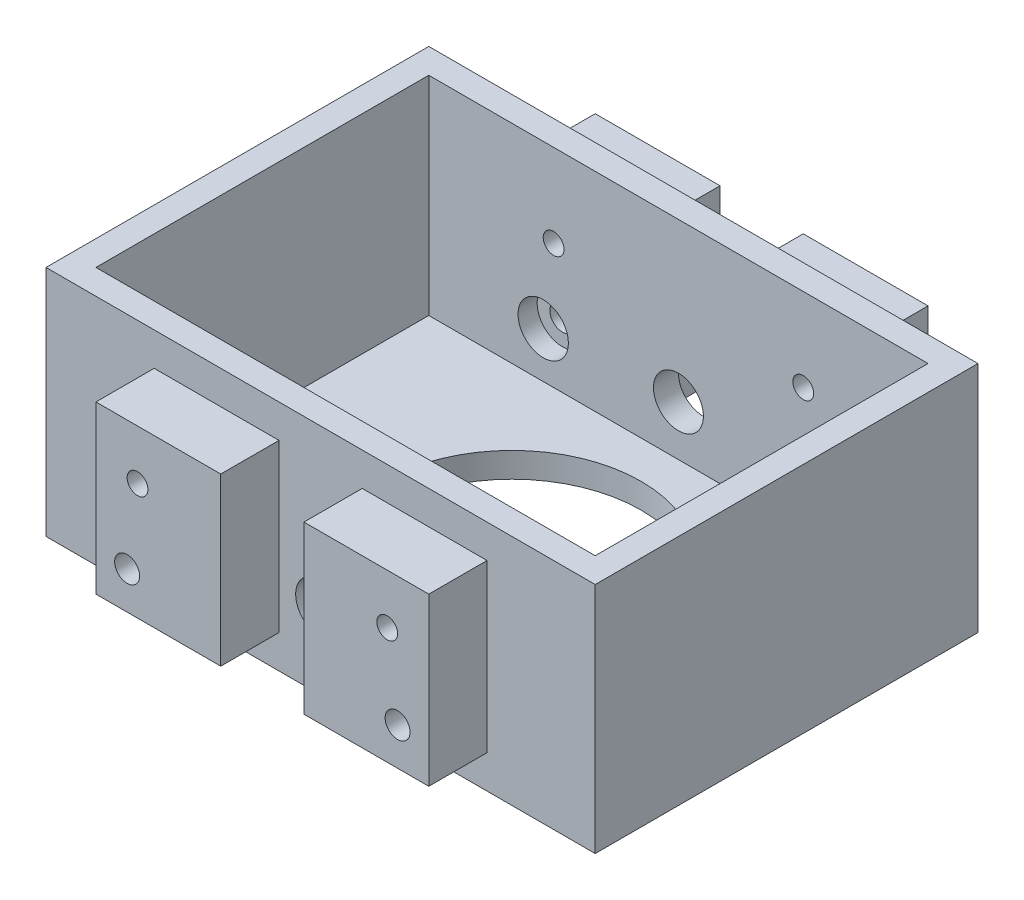
SolidWorks part; units mm, degrees
ref_plane "Front Plane" through (0, 0, 0) normal (0, 0, 1) x (1, 0, 0)
ref_plane "Top Plane" through (0, 0, 0) normal (0, 1, 0) x (1, 0, 0)
ref_plane "Right Plane" through (0, 0, 0) normal (1, 0, 0) x (0, 0, -1)
sketch "Sketch1" plane through (0, 0, 0) normal (0, 1, 0) x (1, 0, 0)
  line L1 (-41.3246, 5.1822) -> (24.6754, 5.1822)
  line L2 (-41.3246, 5.1822) -> (-41.3246, -40.8178)
  line L3 (-41.3246, -40.8178) -> (24.6754, -40.8178)
  line L4 (24.6754, 5.1822) -> (24.6754, -40.8178)
  dimension "D1" = 66
  dimension "D2" = 46
extrude "Boss-Extrude2" add sketch "Sketch1" along normal blind 3
sketch "Sketch3" plane through (0, 3, 0) normal (0, 1, 0) x (1, 0, 0)
  line L0 (-41.3246, 5.1822) -> (-41.3246, -40.8178) construction
  line L1 (-41.3246, 5.1822) -> (-38.3246, 5.1822)
  line L2 (-41.3246, 5.1822) -> (-41.3246, -40.8178)
  line L3 (-41.3246, -40.8178) -> (-38.3246, -40.8178)
  line L4 (-38.3246, 5.1822) -> (-38.3246, -40.8178)
  line L5 (-38.3246, 5.1822) -> (21.6754, 5.1822)
  line L6 (-38.3246, 5.1822) -> (-38.3246, 2.1822)
  line L7 (-38.3246, 2.1822) -> (21.6754, 2.1822)
  line L8 (21.6754, 5.1822) -> (21.6754, 2.1822)
  line L9 (21.6754, 5.1822) -> (24.6754, 5.1822)
  line L10 (21.6754, 5.1822) -> (21.6754, -40.8178)
  line L11 (21.6754, -40.8178) -> (24.6754, -40.8178)
  line L12 (24.6754, 5.1822) -> (24.6754, -40.8178)
  line L13 (-38.3246, -37.8178) -> (21.6754, -37.8178)
  line L14 (-38.3246, -37.8178) -> (-38.3246, -40.8178)
  line L15 (-38.3246, -40.8178) -> (21.6754, -40.8178)
  line L16 (21.6754, -37.8178) -> (21.6754, -40.8178)
  line L17 (24.6754, 5.1822) -> (-41.3246, 5.1822) construction
  line L18 (-41.3246, -40.8178) -> (24.6754, -40.8178) construction
  line L19 (24.6754, -40.8178) -> (24.6754, 5.1822) construction
  point P22 (23.1754, -40.8178)
  dimension "D1" = 3
  dimension "D2" = 3
  dimension "D3" = 3
  dimension "D4" = 3
  dimension "D5" = 0
  dimension "D6" = 0
  dimension "D7" = 0
  dimension "D8" = 0
  dimension "D9" = 0
  dimension "D10" = 0
  dimension "D11" = 0
  dimension "D12" = 0
  dimension "D13" = 0
  dimension "D14" = 0
  dimension "D15" = 0
  dimension "D16" = 0
extrude "Boss-Extrude4" add sketch "Sketch3" along normal blind 25 contours L8 L19 L4 L7 | L4 L19 L0 L17 | L13 L16 L15 L14 | L12 L11 L10 L9 region at (-39.8246, 3, 17.8178) region at (-8.3246, 3, -3.6822)
sketch "Sketch4" plane through (0, 0, 40.8178) normal (0, 0, 1) x (1, 0, 0)
  line L0 (24.6754, 28) -> (24.6754, 0) construction
  line L1 (-13.3246, 24) -> (-28.3246, 24)
  line L2 (-13.3246, 24) -> (-13.3246, 4)
  line L3 (-13.3246, 4) -> (-28.3246, 4)
  line L4 (-28.3246, 24) -> (-28.3246, 4)
  line L5 (-3.3246, 24) -> (11.6754, 24)
  line L6 (-3.3246, 24) -> (-3.3246, 4)
  line L7 (-3.3246, 4) -> (11.6754, 4)
  line L8 (11.6754, 24) -> (11.6754, 4)
  line L10 (-41.3246, 0) -> (24.6754, 0) construction
  line L11 (-41.3246, 28) -> (24.6754, 28) construction
  dimension "D1" = 15
  dimension "D2" = 20
  dimension "D3" = 15
  dimension "D4" = 20
  dimension "D5" = 10
  dimension "D6" = 13
  dimension "D7" = 4
  dimension "D8" = 4
extrude "Boss-Extrude5" add sketch "Sketch4" along normal blind 7 contours L8 L5 L6 L7 | L2 L1 L4 L3 region at (4.1754, 14, 40.8178)
sketch "Sketch5" plane through (0, 0, 47.8178) normal (0, 0, 1) x (1, 0, 0)
  line L0 (-41.3246, 28) -> (-41.3246, 0) construction
  line L1 (-41.3246, 28) -> (24.6754, 28) construction
  line L3 (24.6754, 28) -> (24.6754, 0) construction
  circle A2 centre (-24.5746, 8.5) radius 1.5
  circle A3 centre (7.9254, 8.5) radius 1.5
  circle A4 centre (6.6754, 18) radius 1.25
  circle A5 centre (-23.3246, 18) radius 1.25
  dimension "D5" = 16.75
  dimension "D9" = 3
  dimension "D10" = 2.5
  dimension "D11" = 3
  dimension "D12" = 2.5
  dimension "D1" = 32.5
  dimension "D2" = 30
  dimension "D3" = 9.5
  dimension "D4" = 9.5
  dimension "D6" = 10
  dimension "D7" = 16.75
  dimension "D8" = 18
extrude "Cut-Extrude1" cut sketch "Sketch5" against normal up to next
sketch "Sketch6" plane through (0, 0, -5.1822) normal (0, 0, -1) x (-1, 0, 0)
  line L0 (3.3246, 24) -> (-11.6754, 24)
  line L5 (3.3246, 24) -> (3.3246, 4)
  line L6 (3.3246, 4) -> (-11.6754, 4)
  line L7 (-11.6754, 24) -> (-11.6754, 4)
  line L8 (13.3246, 24) -> (28.3246, 24)
  line L9 (13.3246, 24) -> (13.3246, 4)
  line L10 (13.3246, 4) -> (28.3246, 4)
  line L11 (28.3246, 24) -> (28.3246, 4)
  line L13 (-24.6754, 28) -> (41.3246, 28) construction
  line L14 (41.3246, 28) -> (41.3246, 0) construction
  dimension "D1" = 20
  dimension "D2" = 15
  dimension "D3" = 15
  dimension "D4" = 20
  dimension "D5" = 10
  dimension "D6" = 4
  dimension "D7" = 13
  dimension "D8" = 4
extrude "Boss-Extrude6" add sketch "Sketch6" along normal blind 7 contours L0 L7 L6 L5 | L8 L11 L10 L9 region at (4.1754, 14, -5.1822)
sketch "Sketch7" plane through (0, 0, -12.1822) normal (0, 0, -1) x (-1, 0, 0)
  line L1 (-24.6754, 28) -> (-24.6754, 0) construction
  line L3 (-24.6754, 28) -> (41.3246, 28) construction
  circle A1 centre (-7.9254, 8.5) radius 1.5
  circle A2 centre (24.5746, 8.5) radius 1.5
  circle A3 centre (23.3246, 18) radius 1.25
  circle A4 centre (-6.6754, 18) radius 1.25
  dimension "D5" = 2.5
  dimension "D6" = 3
  dimension "D7" = 2.5
  dimension "D8" = 3
  dimension "D9" = 16.75
  dimension "D10" = 10
  dimension "D11" = 18
  dimension "D12" = 10
  dimension "D1" = 32.5
  dimension "D2" = 9.5
  dimension "D3" = 9.5
  dimension "D4" = 30
extrude "Cut-Extrude2" cut sketch "Sketch7" against normal blind 10
sketch "Sketch8" plane through (0, 0, 0) normal (0, -1, 0) x (-1, 0, 0)
  line L0 (-24.6754, 5.1822) -> (41.3246, 5.1822) construction
  line L1 (41.3246, 5.1822) -> (41.3246, -40.8178) construction
  circle A0 centre (8.3246, -17.8178) radius 15.5
  dimension "D1" = 31
  dimension "D2" = 23
  dimension "D3" = 33
extrude "Cut-Extrude3" cut sketch "Sketch8" against normal up to next contours A0
sketch "Sketch11" plane through (0, 0, 40.8178) normal (0, 0, 1) x (1, 0, 0)
  line L0 (24.6754, 28) -> (24.6754, 0) construction
  line L1 (-41.3246, 0) -> (24.6754, 0) construction
  circle A0 centre (-8.3246, 9) radius 3
  dimension "D1" = 6
  dimension "D2" = 33
  dimension "D3" = 9
extrude "Cut-Extrude6" cut sketch "Sketch11" against normal through all and the other way through all
sketch "Sketch12" plane through (0, 0, 37.8178) normal (0, 0, -1) x (-1, 0, 0)
  circle A0 centre (24.5746, 8.5) radius 3.025
  circle A1 centre (24.5746, 8.5) radius 1.5 construction
  circle A2 centre (-7.9254, 8.5) radius 3.025
  circle A5 centre (-7.9254, 8.5) radius 1.5 construction
  dimension "D1" = 6.05
  dimension "D2" = 6.05
extrude "Cut-Extrude7" cut sketch "Sketch12" against normal blind 2.3
sketch "Sketch14" plane through (0, 0, -2.1822) normal (0, 0, 1) x (1, 0, 0)
  circle A0 centre (-24.5746, 8.5) radius 3.025
  circle A1 centre (-24.5746, 8.5) radius 1.5 construction
  circle A2 centre (7.9254, 8.5) radius 3.025
  circle A3 centre (7.9254, 8.5) radius 1.5 construction
  dimension "D1" = 6.05
  dimension "D2" = 6.05
extrude "Cut-Extrude8" cut sketch "Sketch14" against normal blind 2.3
